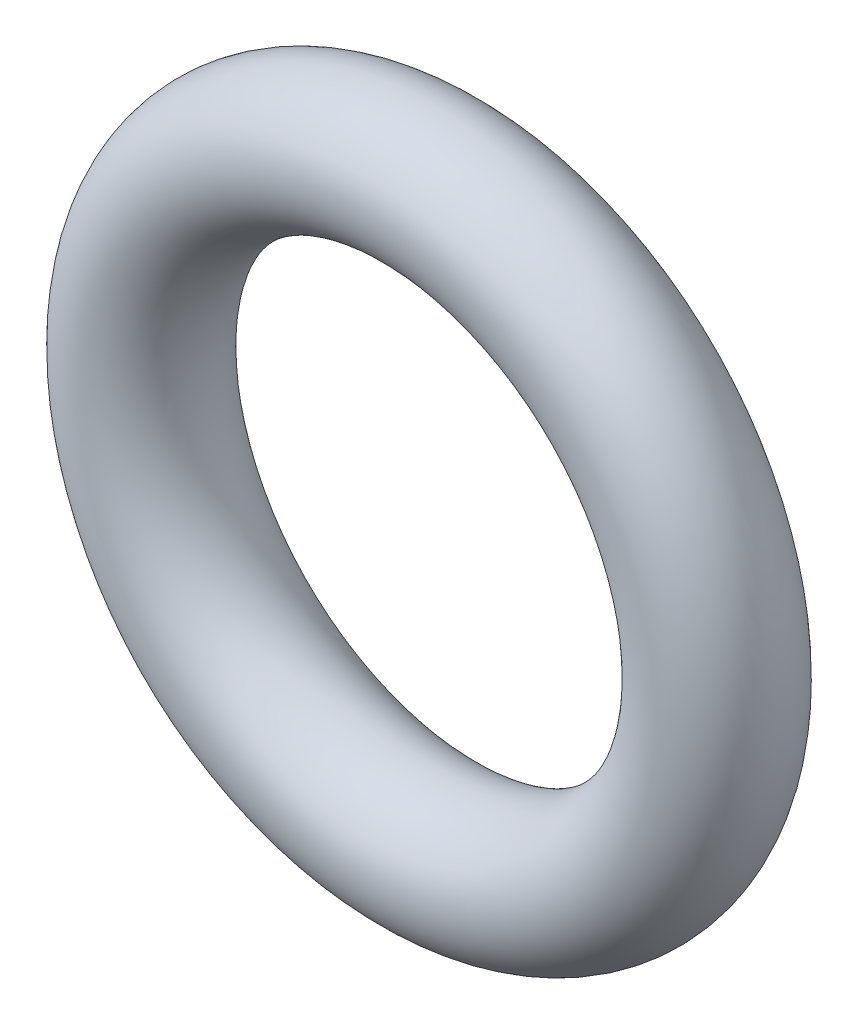
SolidWorks part; units mm, degrees
ref_plane "Top" through (0, 0, 0) normal (0, 0, 1) x (1, 0, 0)
ref_plane "Front" through (0, 0, 0) normal (0, 1, 0) x (1, 0, 0)
ref_plane "Right" through (0, 0, 0) normal (1, 0, 0) x (0, 0, -1)
sketch "O-Ring Sketch" plane through (0, 0, 0) normal (0, 1, 0) x (1, 0, 0)
  line L0 (0, 0) -> (0, 0.5) construction
  line L1 (1.65, -0.5) -> (2.65, -0.5) construction
  line L2 (1.65, -0.5) -> (1.65, 0.5) construction
  line L3 (1.65, 0.5) -> (2.65, 0.5) construction
  line L4 (2.65, -0.5) -> (2.65, 0.5) construction
  line L5 (2.15, 0.5) -> (2.15, -0.5) construction
  line L6 (1.65, 0) -> (2.65, 0) construction
  line L7 (-1.65, -0.5) -> (-1.65, 0.5) construction
  line L8 (-2.65, -0.5) -> (-2.65, 0.5) construction
  circle A0 centre (2.15, 0) radius 0.5
  point P275 (2.15, 0)
  dimension "Inside Diameter" = 3.3
  dimension "Outside Diameter" = 5.3
revolve "O-Ring Revolve" add sketch "O-Ring Sketch" angle 360 about L0
ref_axis "Centerline Axis" [suppressed] through (0, 0, -80.9) along (0, 0, 1)
equation "\"M2 Close Fit Hole\"= 2.2"
equation "\"M2.5 Close Fit Hole\"= 2.7"
equation "\"M3 Close Fit Hole\"= 3.2"
equation "\"M4 Close Fit Hole\"= 4.3"
equation "\"M5 Close Fit Hole\"= 5.3"
equation "\"M6 Close Fit Hole\"= 6.3"
equation "\"M7 Close Fit Hole\"= 7.4"
equation "\"M8 Close Fit Hole\"= 8.4"
equation "\"M2 Tap Hole 75%\"= 1.6"
equation "\"M3 Tap Hole 75%\"= 2.5"
equation "\"M4 Tap Hole 75%\"= 3.3"
equation "\"M5 Tap Hole 75%\"= 4.2"
equation "\"M6 Tap Hole 75%\"= 5"
equation "\"M7 Tap Hole 75%\"= 6"
equation "\"M8 Tap Hole 75%\"= 6.8"
